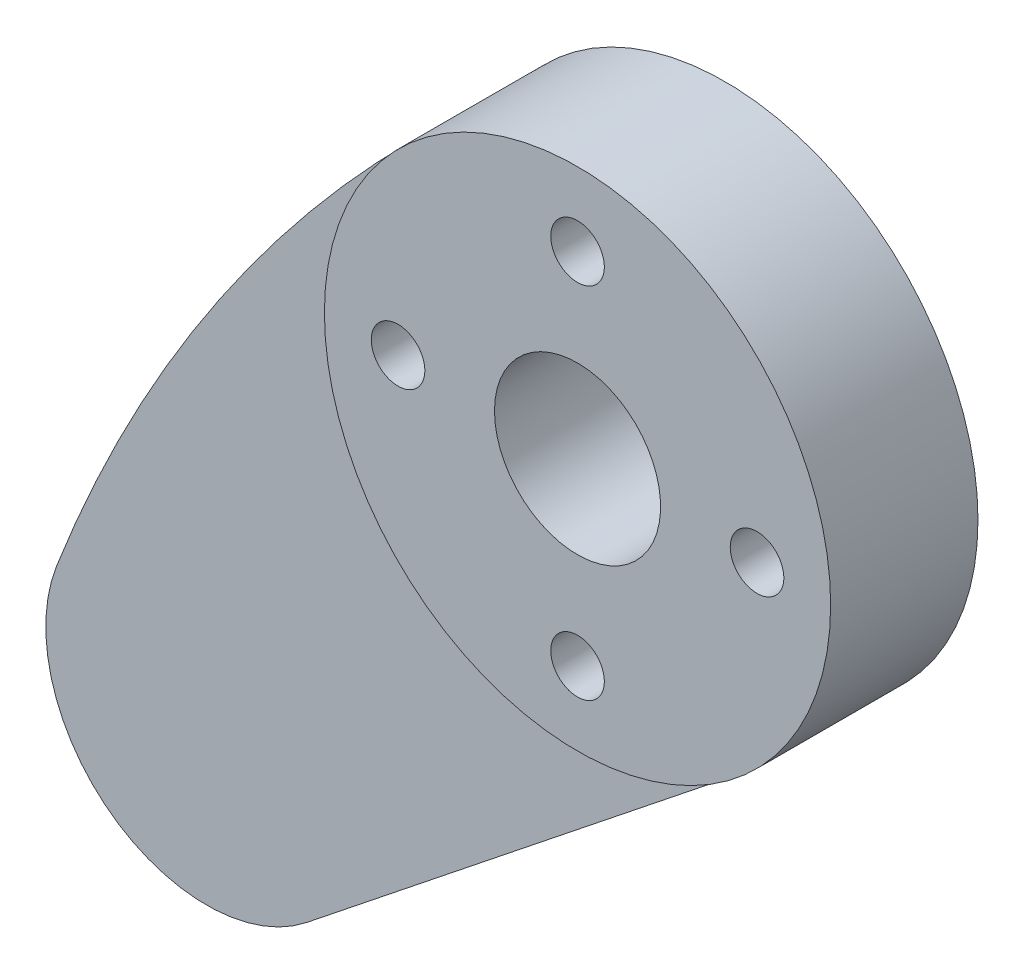
SolidWorks part; units mm, degrees
ref_plane "Front Plane" through (0, 0, 0) normal (0, 0, 1) x (1, 0, 0)
ref_plane "Top Plane" through (0, 0, 0) normal (0, 1, 0) x (1, 0, 0)
ref_plane "Right Plane" through (0, 0, 0) normal (1, 0, 0) x (0, 0, -1)
sketch "Sketch1" plane through (0, 0, 0) normal (0, 0, 1) x (1, 0, 0)
  line L0 (70.1254, 27.305) -> (58.42, 27.305) construction
  line L1 (58.42, 27.305) -> (58.42, 0) construction
  line L2 (58.42, 0) -> (99.06, 0) construction
  line L3 (99.06, 0) -> (99.06, 31.75) construction
  line L4 (99.06, 31.75) -> (73.66, 31.75) construction
  line L5 (73.66, 31.75) -> (73.66, 28.6195) construction
  line L6 (78.6801, 26.924) -> (87.4395, 26.924) construction
  line L7 (87.4395, 26.924) -> (87.4395, 24.13) construction
  line L8 (87.4395, 24.13) -> (80.9328, 22.479) construction
  line L9 (70.1254, 27.305) -> (58.42, 27.305)
  line L10 (58.42, 27.305) -> (58.42, 0)
  line L11 (58.42, 0) -> (99.06, 0)
  line L12 (99.06, 0) -> (99.06, 31.75)
  line L13 (99.06, 31.75) -> (73.66, 31.75)
  line L14 (73.66, 31.75) -> (73.66, 28.6195)
  line L15 (78.6801, 26.924) -> (87.4395, 26.924)
  line L16 (87.4395, 26.924) -> (87.4395, 24.13)
  line L17 (87.4395, 24.13) -> (80.9328, 22.479)
  line L18 (80.8812, 20.7957) -> (87.5941, 20.7957)
  line L19 (87.5941, 20.7957) -> (88.2812, 23.5039)
  line L20 (88.2812, 23.5039) -> (79.7909, 25.6582)
  line L21 (80.9328, 22.479) -> (87.4395, 26.924) construction
  line L22 (88.2812, 23.5039) -> (80.8812, 20.7957) construction
  line L23 (87.5941, 20.7957) -> (79.7909, 25.6582) construction
  line L24 (78.6801, 26.924) -> (87.4395, 24.13) construction
  line L25 (81.3178, 26.0826) -> (111.6739, 61.618) construction
  arc A0 (78.6801, 26.924) -> (73.66, 28.6195) centre (74.168, 21.844) ccw construction
  arc A1 (70.1254, 27.305) -> (80.9328, 22.479) centre (74.168, 21.844) ccw construction
  circle A2 centre (104.4893, 52.0065) radius 12 construction
  arc A3 (78.6801, 26.924) -> (73.66, 28.6195) centre (74.168, 21.844) ccw
  arc A4 (70.1254, 27.305) -> (80.9328, 22.479) centre (74.168, 21.844) ccw
  circle A5 centre (104.4893, 52.0065) radius 12
  circle A6 centre (56.226, 91.417) radius 74.31
  circle A7 centre (86.2672, 31.8764) radius 7.62
  circle A8 centre (148.4954, 7.8931) radius 74.31
  dimension "D2" = 15.24
  dimension "D1" = 46.736
extrude "Boss-Extrude1" add sketch "Sketch1" along normal blind 3.175 contours L13 A7 | L13 A7 L15 L16 | L15 A7 L16 | A7 A6 L12 L13 | A5 A8 A7 L13 L12 A6 | A5 region at (94.0508, 41.3164, 0) region at (104.4893, 52.0065, 0) region at (95.3834, 29.7296, 0) region at (86.5606, 29.0842, 0) region at (84.6642, 25.7868, 0) region at (86.2672, 35.0423, 0)
sketch "Sketch2" plane through (0, 0, 0) normal (0, 0, -1) x (-1, 0, 0)
  circle A0 centre (-104.4893, 52.0065) radius 12
extrude "Boss-Extrude2" add sketch "Sketch2" along normal blind 3.81
sketch "Sketch3" plane through (0, 0, -3.81) normal (0, 0, -1) x (-1, 0, 0)
  circle A1 centre (-104.4893, 52.0065) radius 12
  circle A2 centre (-104.4893, 52.0065) radius 12
  circle A4 centre (-104.4893, 52.0065) radius 3.937
  dimension "D2" = 7.874
  dimension "D1" = 0
extrude "Cut-Extrude1" cut sketch "Sketch3" against normal through all contours A4
sketch "Sketch4" plane through (0, 0, -3.81) normal (0, 0, -1) x (-1, 0, 0)
  line L0 (-104.4893, 60.5155) -> (-104.4893, 52.0065) construction
  line L1 (-104.4893, 52.0065) -> (-104.4893, 43.4975) construction
  line L2 (-104.4893, 52.0065) -> (-95.9803, 52.0065) construction
  line L3 (-104.4893, 52.0065) -> (-112.9983, 52.0065) construction
  circle A1 centre (-104.4893, 52.0065) radius 12
  circle A2 centre (-104.4893, 52.0065) radius 12
  circle A5 centre (-104.4893, 52.0065) radius 8.509 construction
  circle A6 centre (-95.9803, 52.0065) radius 1.27
  circle A7 centre (-112.9983, 52.0065) radius 1.27
  circle A8 centre (-104.4893, 43.4975) radius 1.27
  circle A9 centre (-104.4893, 60.5155) radius 1.27
  dimension "D2" = 17.018
  dimension "D3" = 2.54
  dimension "D1" = 0
extrude "Cut-Extrude2" cut sketch "Sketch4" against normal through all contours A7 | A6 | A9 | A8 region at (95.9803, 52.0065, -3.81) region at (112.9983, 52.0065, -3.81)
sketch "Sketch5" plane through (0, 0, 0) normal (0, 0, -1) x (-1, 0, 0)
  arc A0 (-113.7841, 44.4166) -> (-96.0143, 60.5021) centre (-104.4893, 52.0065) ccw construction
  arc A1 (-113.7841, 44.4166) -> (-89.6997, 25.0733) centre (-56.226, 91.417) ccw construction
  arc A2 (-89.6997, 25.0733) -> (-79.157, 34.6168) centre (-86.2672, 31.8764) ccw construction
  arc A3 (-79.157, 34.6168) -> (-96.0143, 60.5021) centre (-148.4954, 7.8931) ccw construction
  circle A4 centre (-104.4893, 52.0065) radius 12 construction
  arc A5 (-113.7841, 44.4166) -> (-96.0143, 60.5021) centre (-104.4893, 52.0065) ccw
  arc A6 (-113.7841, 44.4166) -> (-89.6997, 25.0733) centre (-56.226, 91.417) ccw
  arc A7 (-89.6997, 25.0733) -> (-79.157, 34.6168) centre (-86.2672, 31.8764) ccw
  arc A8 (-79.157, 34.6168) -> (-96.0143, 60.5021) centre (-148.4954, 7.8931) ccw
  circle A9 centre (-104.4893, 52.0065) radius 12
  circle A10 centre (-86.2672, 31.8764) radius 7.62
  circle A11 centre (-104.4893, 52.0065) radius 12
  arc A12 (-93.8135, 30.8191) -> (-104.4305, 40.0066) centre (-104.3783, 29.3388) ccw
  arc M2 (-113.7841, 44.4166) -> (-89.6997, 25.0733) centre (-56.226, 91.417) ccw
  dimension "D1" = 10.668
extrude "Cut-Extrude3" cut sketch "Sketch5" against normal through all contours A10 A12 A11 M2 region at (100.4293, 35.0094, 0)
sketch "Sketch6" plane through (0, 0, 3.175) normal (0, 0, 1) x (1, 0, 0)
  arc A4 (79.157, 34.6168) -> (93.8135, 30.8191) centre (86.2672, 31.8764) ccw
  arc A5 (104.4305, 40.0066) -> (93.8135, 30.8191) centre (104.3783, 29.3388) ccw
  arc A6 (104.4305, 40.0066) -> (96.0143, 60.5021) centre (104.4893, 52.0065) ccw
  arc A7 (96.0143, 60.5021) -> (79.157, 34.6168) centre (148.4954, 7.8931) ccw
  arc A8 (79.157, 34.6168) -> (93.8135, 30.8191) centre (86.2672, 31.8764) ccw
  arc A9 (104.4305, 40.0066) -> (93.8135, 30.8191) centre (104.3783, 29.3388) ccw
  arc A10 (104.4305, 40.0066) -> (96.0143, 60.5021) centre (104.4893, 52.0065) ccw
  arc A11 (96.0143, 60.5021) -> (79.157, 34.6168) centre (148.4954, 7.8931) ccw
  circle A20 centre (104.4893, 52.0065) radius 12
  arc M10 (79.157, 34.6168) -> (93.8135, 30.8191) centre (86.2672, 31.8764) ccw
  arc M11 (93.8135, 30.8191) -> (104.4305, 40.0066) centre (104.3783, 29.3388) cw
  arc M13 (96.0143, 60.5021) -> (79.157, 34.6168) centre (148.4954, 7.8931) ccw
  dimension "D1" = 0
extrude "Cut-Extrude4" cut sketch "Sketch6" against normal blind 0.635 contours A20 M13 M10 M11 region at (88.5334, 37.6679, 3.175)
sketch "Sketch7" plane through (0, 0, 2.54) normal (0, 0, 1) x (1, 0, 0)
  line L0 (91.0175, 25.9184) -> (111.9701, 42.6237)
  circle A0 centre (104.4893, 52.0065) radius 12 construction
  arc A1 (96.0143, 60.5021) -> (104.4305, 40.0066) centre (104.4893, 52.0065) ccw construction
  arc A2 (96.0143, 60.5021) -> (79.157, 34.6168) centre (148.4954, 7.8931) ccw construction
  arc A3 (79.157, 34.6168) -> (93.8135, 30.8191) centre (86.2672, 31.8764) ccw construction
  arc A4 (104.4305, 40.0066) -> (93.8135, 30.8191) centre (104.3783, 29.3388) ccw construction
  circle A5 centre (104.4893, 52.0065) radius 12
  arc A6 (96.0143, 60.5021) -> (104.4305, 40.0066) centre (104.4893, 52.0065) ccw
  arc A7 (96.0143, 60.5021) -> (79.157, 34.6168) centre (148.4954, 7.8931) ccw
  arc A8 (79.157, 34.6168) -> (93.8135, 30.8191) centre (86.2672, 31.8764) ccw
  arc A9 (104.4305, 40.0066) -> (93.8135, 30.8191) centre (104.3783, 29.3388) ccw
  arc M4 (79.157, 34.6168) -> (93.8135, 30.8191) centre (86.2672, 31.8764) ccw
  arc M5 (93.8135, 30.8191) -> (104.4305, 40.0066) centre (104.3783, 29.3388) cw
extrude "Boss-Extrude3" add sketch "Sketch7" against normal up to surface (2.54 mm away) contours A5 L0 M5 M4 region at (99.791, 35.4155, 2.54) up to face at (95.5495, 40.6036, 0)
